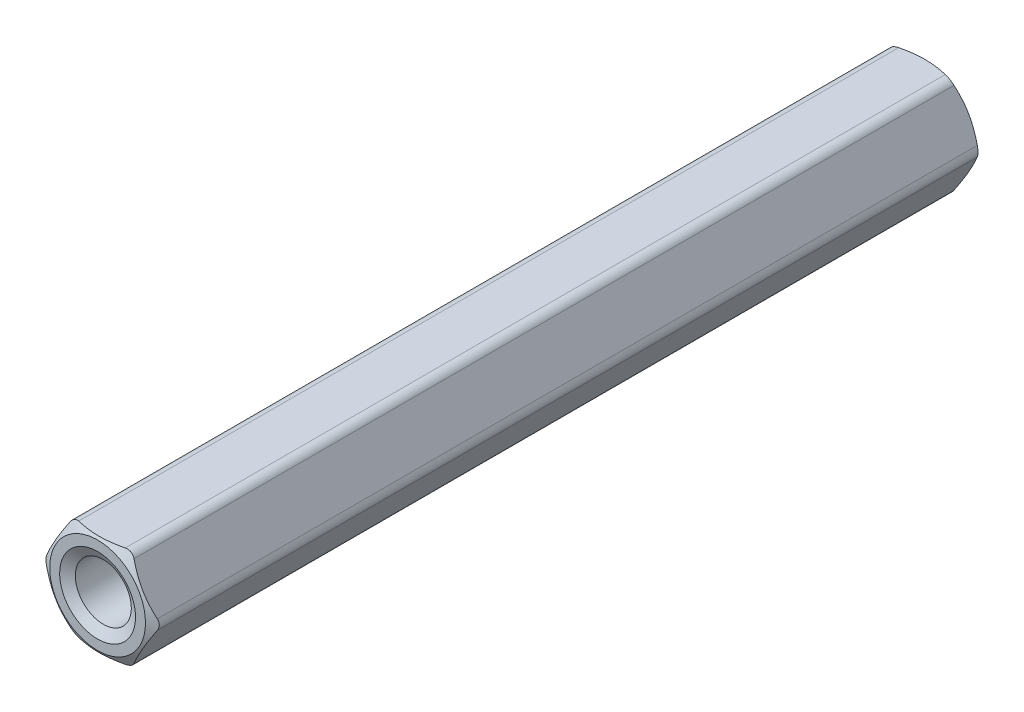
SolidWorks part; units mm, degrees
ref_plane "Front Plane" through (0, 0, 0) normal (0, 0, 1) x (1, 0, 0)
ref_plane "Top Plane" through (0, 0, 0) normal (0, 1, 0) x (1, 0, 0)
ref_plane "Right Plane" through (0, 0, 0) normal (1, 0, 0) x (0, 0, -1)
sketch "Sketch1" plane through (0, 0, 0) normal (0, 0, 1) x (1, 0, 0)
  line L0 (0, 0) -> (2.5981, 0) construction
  line L1 (1.299, -2.25) -> (2.5981, 0)
  line L2 (2.5981, 0) -> (1.299, 2.25)
  line L3 (1.299, 2.25) -> (-1.299, 2.25)
  line L4 (-1.299, 2.25) -> (-2.5981, 0)
  line L5 (-2.5981, 0) -> (-1.299, -2.25)
  line L6 (-1.299, -2.25) -> (1.299, -2.25)
  circle A0 centre (0, 0) radius 2.25 construction
  point P10 (0, -2.25)
  dimension "Hex Size" = 4.5
sketch "Sketch2" plane through (0, 0, 0) normal (1, 0, 0) x (0, 0, -1)
  line L0 (-13.7, 0) -> (-18.5, 0) construction
  line L3 (-13.7, 1.25) -> (-13.7, -1.25) construction
  line L4 (-18.9219, 1.2987) -> (-18.6969, 0.909) construction
  line L5 (-18.6969, 0.909) -> (-18.4719, 1.2987) construction
  line L6 (-18.4719, 1.2987) -> (-18.9219, 1.2987) construction
  line L7 (-18.8937, 1.25) -> (-18.5, 1.25) construction
  line L8 (-18.725, 0.9577) -> (-18.6687, 0.9577) construction
  line L9 (-18.6969, 0.9577) -> (-18.6969, 0.909) construction
  line L10 (-18.6969, 1.25) -> (-18.6969, 1.2987) construction
  line L11 (18.5, 2.25) -> (-18.5, 2.25) construction
  point P6 (0, 2.25)
  point P9 (-13.7, 0)
  dimension "Minimum Thread Length" = 4.8
  dimension "Thread Size" = 2.5
  dimension "Thread Pitch" = 0.45
  dimension "Thread Pitch (B)/8" = 0.0563
  dimension "Length" = 37
sketch "Sketch3" plane through (0, 0, 0) normal (1, 0, 0) x (0, 0, -1)
  line L1 (-13.7, 1.25) -> (-13.7, 0)
  line L2 (18.5, 2.25) -> (18.5, 1.6937)
  line L3 (18.5, 1.6937) -> (18.2438, 1.25)
  line L6 (18.5, 2.25) -> (18.5, 1.6937)
  line L8 (18.2438, 1.25) -> (13.7, 1.25)
  line L9 (-18.2438, 1.25) -> (-18.5, 1.6937)
  line L10 (0, 2.25) -> (18.5, 2.25)
  line L11 (-18.5, 1.6937) -> (-18.5, 2.25)
  line L12 (-18.5, 2.25) -> (0, 2.25)
  line L13 (-18.5, 2.1375) -> (-18.5, -2.1375) construction
  line L15 (-18.2438, 1.25) -> (-18.2438, 1.5458) construction
  line L16 (-18.2438, 1.5458) -> (-18.2438, 1.8417) construction
  line L17 (-18.2438, 1.8417) -> (-18.2438, 2.1375) construction
  line L18 (-18.2682, 1.2922) -> (-18.2438, 1.25) construction
  line L19 (-18.6969, 1.25) -> (-18.6969, 1.2987) construction
  line L20 (-13.7, 0) -> (13.7, 0)
  line L21 (13.7, 0) -> (13.7, 1.25)
  line L22 (-13.7, 1.25) -> (-18.2438, 1.25)
  point P5 (-18.5, -2.25)
  point P15 (-18.2438, 1.6937)
  point P20 (-18.2682, 1.2922)
  dimension "D1" = 60
  dimension "D3" = 4.275
revolve "Revolve1" add sketch "Sketch3" angle 360 about L0
sketch "Sketch4" plane through (0, 0, 0) normal (0, 0, 1) x (1, 0, 0)
  line L0 (0, 2.25) -> (0, 1.25) construction
  line L1 (-1.299, 2.25) -> (-2.5981, 0)
  line L2 (-2.5981, 0) -> (-1.299, -2.25)
  line L3 (-1.299, -2.25) -> (1.299, -2.25)
  line L4 (1.299, -2.25) -> (2.5981, 0)
  line L5 (2.5981, 0) -> (1.299, 2.25)
  line L6 (1.299, 2.25) -> (-1.299, 2.25)
  line L7 (1.299, -2.25) -> (2.5981, 0) construction
  circle A0 centre (0, 0) radius 2.25 construction
  circle A1 centre (0, 0) radius 1.75
  circle A2 centre (0, 0) radius 2.25 construction
  point P16 (0, 1.75)
extrude "Boss-Extrude1" add sketch "Sketch4" against normal mid plane 37
sketch "Sketch5" plane through (0, 0, 18.5) normal (0, 0, 1) x (1, 0, 0)
  line L0 (0, 1.25) -> (0, -1.25) construction
  line L1 (0, 1.25) -> (0, -1.25) construction
  circle A0 centre (0, 0) radius 2.1375
  point P11 (0, -1.25)
extrude "Cut-Extrude1" cut sketch "Sketch5" against normal through all draft 60 flip side to cut
sketch "Sketch6" plane through (0, 0, -18.5) normal (0, 0, -1) x (-1, 0, 0)
  circle A0 centre (0, 0) radius 2.1375
  circle A1 centre (0, 0) radius 2.1375 construction
extrude "Cut-Extrude2" cut sketch "Sketch6" against normal through all draft 60 flip side to cut
fillet "Fillet1" radius 0.45 6 edges at (1.299, 2.25, 0) (-2.5981, 0, 0) (-1.299, -2.25, 0) (1.299, -2.25, 0) (2.5981, 0, 0) (-1.299, 2.25, 0)
sketch "Drawing 1" plane through (0, 0, 0) normal (1, 0, 0) x (0, 0, -1)
  line L0 (-13.7, -1.25) -> (-18.5, -1.25) construction
  line L1 (-13.7, 1.25) -> (-18.5, 1.25) construction
  line L2 (-13.7, 1.25) -> (-13.7, -1.25) construction
  line L3 (-13.7, 0) -> (-18.5, 0) construction
  line L4 (18.5, 1.25) -> (13.7, 1.25) construction
  line L5 (13.7, 1.25) -> (13.7, -1.25) construction
  line L6 (13.7, -1.25) -> (18.5, -1.25) construction
sketch "Sketch7" [suppressed] plane through (0, 0, 0) normal (0, 0, -1) x (-1, 0, 0)
  circle A0 centre (0, 0) radius 1.6937
extrude "Boss-Extrude2" [suppressed] add sketch "Sketch7" along normal up to surface (18.5 mm away)
other "SurfaceCut1" [suppressed]
sketch "Sketch8" [suppressed] plane through (0, 0, 0) normal (1, 0, 0) x (0, 0, -1)
  line L0 (-13.7, 0) -> (-18.5, 0) construction
  line L1 (-13.7, 1.25) -> (-18.5, 1.25)
  line L2 (-13.7, 1.25) -> (-13.7, 0)
  line L3 (-13.7, 0) -> (-18.5, 0)
  line L4 (-18.5, 1.25) -> (-18.5, 0)
revolve "Revolve2" [suppressed] add sketch "Sketch8" angle 360 about L0
sketch "Sketch9" [suppressed] plane through (0, 0, 18.5) normal (0, 0, 1) x (1, 0, 0)
  circle A0 centre (0, 0) radius 1.25
  circle A1 centre (0, 0) radius 1.25 construction
sketch "Sketch10" [suppressed] plane through (0, 0, 0) normal (1, 0, 0) x (0, 0, -1)
  line L0 (-18.725, 0.9577) -> (-18.6687, 0.9577)
  line L1 (-18.6687, 0.9577) -> (-18.4859, 1.2744)
  line L2 (-18.6969, 0.909) -> (-18.4719, 1.2987) construction
  line L3 (-18.4859, 1.2744) -> (-18.9078, 1.2744)
  line L4 (-18.9219, 1.2987) -> (-18.6969, 0.909) construction
  line L5 (-18.9078, 1.2744) -> (-18.725, 0.9577)
  line L6 (-18.6969, 1.25) -> (-18.6969, 1.2987) construction
  point P12 (-18.6969, 1.2744)
curve "Helix/Spiral1" [suppressed] pitch 0.45 height 4.05 turns 9
sweep "Cut-Sweep1" [suppressed] cut profiles "Sketch10" path "Helix/Spiral1"
pattern_linear "LPattern1" [suppressed] count 2 spacing 3.15 of bodies 114
combine bodies "Combine1" [suppressed] operation type subtract main body 113 bodies to subtract 119
ref_plane "Plane1" [suppressed] through (0, 0, 18.2682) normal (0, 0, 1) x (1, 0, 0)
sketch "Sketch11" [suppressed] plane through (0, 0, 18.5) normal (0, 0, 1) x (1, 0, 0)
  circle A0 centre (0, 0) radius 1.6937
extrude "Cut-Extrude3" [suppressed] cut sketch "Sketch11" against normal through all draft 60
sketch "Sketch12" [suppressed] plane through (0, 0, 18.2682) normal (0, 0, 1) x (1, 0, 0)
  circle A0 centre (0, 0) radius 1.3008
  circle A1 centre (0, 0) radius 1.25 construction
  dimension "D1" = 0.0508
extrude "Cut-Extrude4" [suppressed] cut sketch "Sketch12" against normal through all draft 45
pattern_circular "CirPattern1" [suppressed] count 2 over 360 about axis through (0, 0, 0) along (1, 0, 0) of bodies 118
combine bodies "Combine2" [suppressed] bodies to combine 118 122
ref_axis "Z" through (0, 0, 20.35) along (0, 0, -1)
ref_point "Point2"
equation "\"Thread Pitch (B)/8@Sketch2\" = \"Thread Pitch@Sketch2\" / 8"
equation "\"D1@Fillet1\" = \"Hex Size@Sketch1\" * .1"
equation "\"D3@Helix/Spiral1\" = \"segment length\" + \"Thread Pitch@Sketch2\""
equation "\"D4@Helix/Spiral1\" = \"Thread Pitch@Sketch2\""
equation "\"D1@Boss-Extrude1\" = \"Length@Sketch2\""
equation "\"thread count\"= \"Minimum Thread Length@Sketch2\" * .75 / \"Thread Pitch@Sketch2\""
equation "\"rounded thread count\"= IIF ( \"thread count\" - int ( \"thread count\" ) > 0 , int ( \"thread count\" ) + 1 , \"thread count\" )"
equation "\"segment length\"= \"Thread Pitch@Sketch2\" * \"rounded thread count\""
equation "\"D3@LPattern1\" = \"segment length\" - \"Thread Pitch@Sketch2\""
equation "\"D3@Cut-Extrude3\"=\"D1@Sketch3\""
equation "\"D3@Sketch3\"=\"Hex Size@Sketch1\"*.95"
